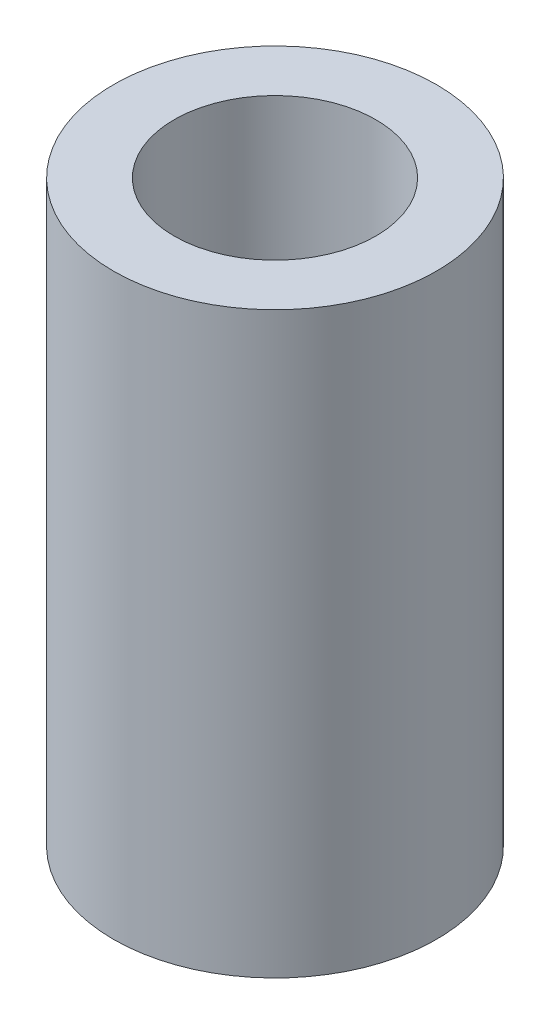
SolidWorks part; units mm, degrees
ref_plane "Front Plane" through (0, 0, 0) normal (0, 0, 1) x (1, 0, 0)
ref_plane "Top Plane" through (0, 0, 0) normal (0, 1, 0) x (1, 0, 0)
ref_plane "Right Plane" through (0, 0, 0) normal (1, 0, 0) x (0, 0, -1)
sketch "Sketch1" plane through (0, 0, 0) normal (0, 1, 0) x (1, 0, 0)
  circle A0 centre (0, 0) radius 20
  dimension "SLEEVE_OD" = 40
extrude "Boss-Extrude1" add sketch "Sketch1" along normal blind 71.6548
sketch "Sketch2" plane through (0, 0, 0) normal (0, 1, 0) x (1, 0, 0)
  circle A0 centre (0, 0) radius 12.4875
  dimension "BORE_D" = 24.975
extrude "Cut-Extrude1" cut sketch "Sketch2" along normal through all
chamfer "Chamfer1" distance 3.1628 angle 66.281 rebuild error yes
